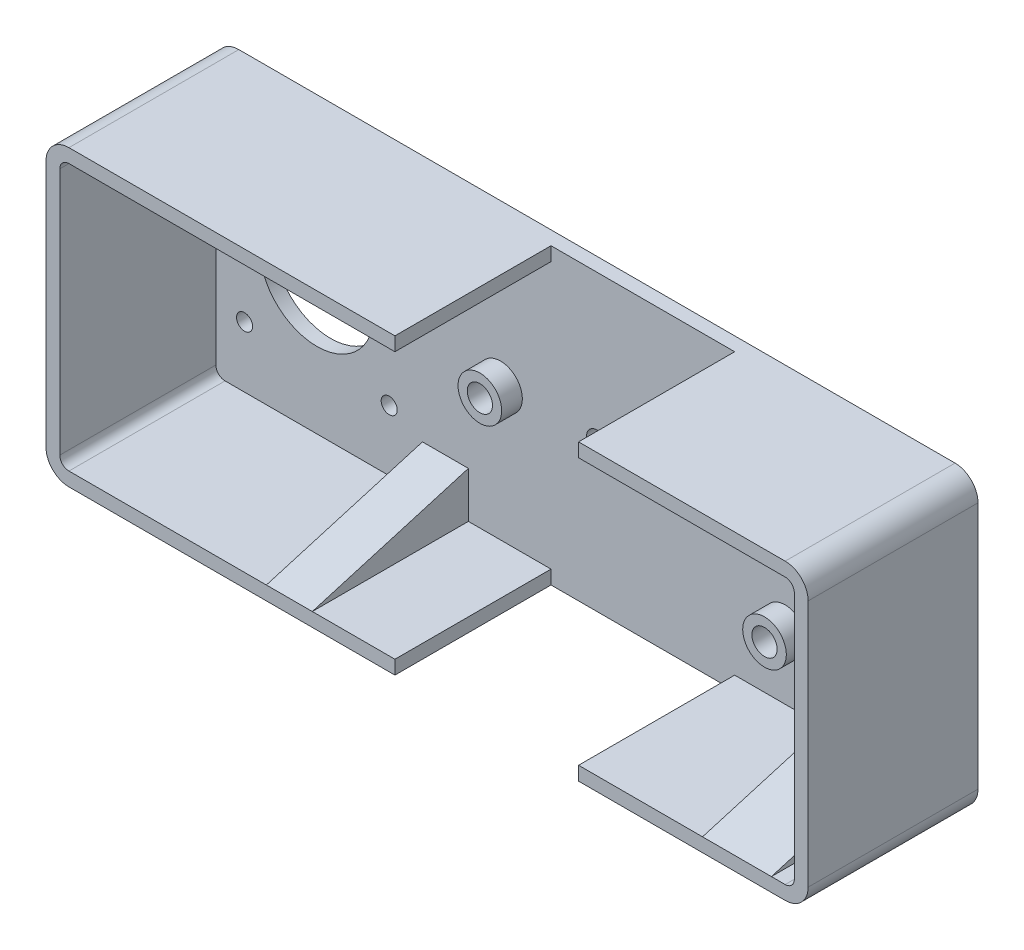
SolidWorks part; units mm, degrees
ref_plane "Front Plane" through (0, 0, 0) normal (0, 0, 1) x (1, 0, 0)
ref_plane "Top Plane" through (0, 0, 0) normal (0, 1, 0) x (1, 0, 0)
ref_plane "Right Plane" through (0, 0, 0) normal (1, 0, 0) x (0, 0, -1)
sketch "Sketch1" plane through (0, 0, 0) normal (0, 0, 1) x (1, 0, 0)
  line L1 (-78, 32) -> (78, 32)
  line L2 (-83, 27) -> (-83, -27)
  line L3 (-78, -32) -> (78, -32)
  line L4 (83, 27) -> (83, -27)
  line L5 (-83, 32) -> (83, -32) construction
  line L6 (-83, -32) -> (83, 32) construction
  arc A0 (78, -32) -> (83, -27) centre (78, -27) ccw
  arc A1 (78, 32) -> (83, 27) centre (78, 27) cw
  arc A2 (-83, -27) -> (-78, -32) centre (-78, -27) ccw
  arc A3 (-78, 32) -> (-83, 27) centre (-78, 27) ccw
  point P0 (0, 0)
  dimension "D3" = 5
  dimension "D1" = 64
  dimension "D2" = 166
extrude "Boss-Extrude1" add sketch "Sketch1" along normal blind 37
sketch "Sketch2" plane through (0, 0, 37) normal (0, 0, 1) x (1, 0, 0)
  line L0 (-58, 0) -> (0, 0) construction
  line L1 (-42.25, 15.75) -> (-73.75, 15.75) construction
  line L2 (-42.25, 15.75) -> (-42.25, -15.75) construction
  line L3 (-42.25, -15.75) -> (-73.75, -15.75) construction
  line L4 (-73.75, 15.75) -> (-73.75, -15.75) construction
  line L5 (-42.25, 15.75) -> (-73.75, -15.75) construction
  line L6 (-42.25, -15.75) -> (-73.75, 15.75) construction
  line L7 (-83, 27) -> (-83, -27) construction
  line L8 (44, 15) -> (44, -15) construction
  line L9 (0, 0) -> (44, 0) construction
  line L10 (44, 0) -> (64, 0) construction
  circle A0 centre (-73.75, 15.75) radius 1.75
  circle A1 centre (-42.25, 15.75) radius 1.75
  circle A2 centre (-73.75, -15.75) radius 1.75
  circle A3 centre (-42.25, -15.75) radius 1.75
  circle A4 centre (-58, 0) radius 12.5
  circle A5 centre (44, 15) radius 2.75
  circle A6 centre (44, -15) radius 2.75
  circle A7 centre (-18, 0) radius 2.75
  circle A8 centre (64, 0) radius 2.25
  point P0 (-58, 0)
  dimension "D1" = 3.5
  dimension "D4" = 25
  dimension "D5" = 5.5
  dimension "D10" = 4.5
  dimension "D2" = 31.5
  dimension "D3" = 25
  dimension "D6" = 30
  dimension "D7" = 127
  dimension "D8" = 62
  dimension "D9" = 20
extrude "Cut-Extrude1" cut sketch "Sketch2" against normal through all
sketch "Sketch3" plane through (0, 0, 37) normal (0, 0, 1) x (1, 0, 0)
  circle A3 centre (44, 15) radius 2.75 construction
  circle A4 centre (44, 15) radius 2.75
  circle A5 centre (44, 15) radius 4.75
  circle A6 centre (-18, 0) radius 2.75 construction
  circle A7 centre (44, -15) radius 2.75 construction
  circle A8 centre (-18, 0) radius 2.75
  circle A9 centre (44, -15) radius 2.75
  circle A10 centre (-18, 0) radius 4.75
  circle A11 centre (44, -15) radius 4.75
  dimension "D1" = 2
  dimension "D2" = 2
sketch "Sketch4" plane through (0, 0, 0) normal (0, 0, 1) x (1, 0, 0)
  line L0 (83, 10) -> (83, -10)
  line L1 (83, -27) -> (83, 27) construction
  line L2 (0, 0) -> (83, 0) construction
  line L3 (83, 10) -> (93, 10)
  line L4 (83, -10) -> (93, -10)
  line L5 (93, 10) -> (93, -10) construction
  arc A0 (93, -10) -> (93, 10) centre (93, 0) ccw
  circle A1 centre (93, 0) radius 2.25
  dimension "D3" = 4.5
  dimension "D1" = 20
  dimension "D2" = 10
sketch "Sketch5" plane through (0, 0, 37) normal (0, 0, 1) x (1, 0, 0)
  line L0 (-18, 0) -> (44, 0) construction
  line L1 (44, 0) -> (44, -15) construction
  circle A0 centre (3, 0) radius 2.25
  circle A1 centre (23, 0) radius 2.25
  point P10 (13, 0)
  dimension "D3" = 4.5
  dimension "D1" = 10
  dimension "D2" = 10
extrude "Cut-Extrude2" cut sketch "Sketch5" against normal through all
sketch "Sketch6" plane through (0, 0, 37) normal (0, 0, 1) x (1, 0, 0)
  line L0 (78, 32) -> (-78, 32) construction
  line L1 (-78, -29) -> (78, -29)
  line L2 (-80, -27) -> (-80, 27)
  line L3 (-78, 29) -> (78, 29)
  line L4 (80, -27) -> (80, 27)
  line L5 (-80, -29) -> (80, 29) construction
  line L6 (-80, 29) -> (80, -29) construction
  line L7 (83, -27) -> (83, 27) construction
  arc A0 (-80, 27) -> (-78, 29) centre (-78, 27) cw
  arc A1 (-78, -29) -> (-80, -27) centre (-78, -27) cw
  arc A2 (78, -29) -> (80, -27) centre (78, -27) ccw
  arc A3 (78, 29) -> (80, 27) centre (78, 27) cw
  point P0 (0, 0)
  dimension "D3" = 2
  dimension "D1" = 3
  dimension "D2" = 3
extrude "Cut-Extrude3" cut sketch "Sketch6" against normal blind 34
sketch "Sketch7" plane through (0, 0, 3) normal (0, 0, 1) x (1, 0, 0)
  circle A0 centre (-18, 0) radius 4.75
  circle A1 centre (-18, 0) radius 2.75 construction
  circle A2 centre (44, -15) radius 4.75
  circle A3 centre (44, 15) radius 4.75
  circle A4 centre (44, -15) radius 2.75 construction
  dimension "D1" = 2
  dimension "D2" = 2
  dimension "D3" = 9.5
extrude "Boss-Extrude2" add sketch "Sketch7" along normal blind 4.5
sketch "Sketch10" plane through (0, 0, 37) normal (0, 0, 1) x (1, 0, 0)
  line L0 (-78, -32) -> (78, -32) construction
  line L1 (-7, -32) -> (33, -32)
  line L2 (-7, -32) -> (-7, 32)
  line L3 (-7, 32) -> (33, 32)
  line L4 (33, -32) -> (33, 32)
  line L5 (-7, -32) -> (33, 32) construction
  line L6 (-7, 32) -> (33, -32) construction
  line L7 (78, 32) -> (-78, 32) construction
  line L8 (13, 0) -> (44, 0) construction
  line L9 (0, 0) -> (83, 0) construction
  line L10 (44, 0) -> (44, -15) construction
  point P0 (13, 0)
  point P20 (80, 10)
  point P22 (77, -9.8749)
  point P25 (0, 0)
  point P26 (0, 0)
  dimension "D1" = 40
  dimension "D2" = 31
extrude "Cut-Extrude4" cut sketch "Sketch10" against normal blind 34
sketch "Sketch11" plane through (0, 0, 7.5) normal (0, 0, 1) x (1, 0, 0)
  circle A0 centre (44, -15) radius 2.75
  circle A1 centre (-18, 0) radius 2.75
  circle A2 centre (44, 15) radius 2.75
  dimension "D1" = 5.5
  dimension "D2" = 5.5
  dimension "D3" = 5.5
extrude "Cut-Extrude5" cut sketch "Sketch11" against normal through all
sketch "Sketch12" plane through (0, 0, 3) normal (0, 0, 1) x (1, 0, 0)
  line L0 (33, -29) -> (78, -29) construction
  line L1 (60, -29) -> (75, -29)
  line L2 (60, -29) -> (60, -19)
  line L3 (60, -19) -> (75, -19)
  line L4 (75, -29) -> (75, -19)
  line L5 (83, 0) -> (32.1507, 0) construction
  line L6 (0, 0) -> (83, 0) construction
  line L7 (60, 19) -> (75, 19)
  line L8 (75, 29) -> (75, 19)
  line L9 (60, 29) -> (75, 29)
  line L10 (60, 29) -> (60, 19)
  line L11 (80, -27) -> (80, 27) construction
  line L12 (80, -6) -> (60, -6)
  line L13 (80, -6) -> (80, -16)
  line L14 (80, -16) -> (60, -16)
  line L15 (60, -6) -> (60, -16)
  line L16 (80, 16) -> (60, 16)
  line L17 (60, 6) -> (60, 16)
  line L18 (80, 6) -> (60, 6)
  line L19 (80, 6) -> (80, 16)
  line L20 (80, -27) -> (80, 27) construction
  line L21 (-78, -29) -> (-7, -29) construction
  line L22 (-35, -29) -> (-25, -29)
  line L23 (-35, -29) -> (-35, -19)
  line L24 (-35, -19) -> (-25, -19)
  line L25 (-25, -29) -> (-25, -19)
  line L26 (-35, 19) -> (-25, 19)
  line L27 (-25, 29) -> (-25, 19)
  line L28 (-35, 29) -> (-25, 29)
  line L29 (-35, 29) -> (-35, 19)
  line L30 (-80, 27) -> (-80, -27) construction
  dimension "D1" = 15
  dimension "D2" = 5
  dimension "D3" = 10
  dimension "D4" = 20
  dimension "D5" = 3
  dimension "D6" = 10
  dimension "D7" = 10
  dimension "D8" = 10
  dimension "D9" = 45
extrude "Boss-Extrude3" add sketch "Sketch12" along normal through all
sketch "Sketch14" plane through (0, -16, 0) normal (0, -1, 0) x (1, 0, 0)
  line L3 (80, 37) -> (60, 37)
  line L4 (60, 37) -> (60, 3)
  line L5 (60, 3) -> (80, 37)
  dimension "D1" = 34
extrude "Cut-Extrude6" cut sketch "Sketch14" against normal blind 33
sketch "Sketch16" plane through (75, 0, 0) normal (1, 0, 0) x (0, 0, -1)
  line L0 (-37, -19) -> (-3, -19)
  line L1 (-3, -19) -> (-37, -29)
  line L2 (-37, -27) -> (-37, 27) construction
  line L3 (-37, -29) -> (-37, -19)
  point P3 (-37, -22.6292)
  point P7 (-37, -34)
  dimension "D1" = 10
  dimension "D2" = 34
extrude "Cut-Extrude8" cut sketch "Sketch16" against normal blind 15
sketch "Sketch17" plane through (60, 0, 0) normal (-1, 0, 0) x (0, 0, 1)
  line L6 (37, 19) -> (3, 19)
  line L7 (3, 19) -> (37, 29)
  line L8 (37, 29) -> (37, 19)
extrude "Cut-Extrude9" cut sketch "Sketch17" against normal blind 15
sketch "Sketch18" plane through (-25, 0, 0) normal (1, 0, 0) x (0, 0, -1)
  line L0 (-37, -29) -> (-37, -19)
  line L1 (-37, -19) -> (-3, -19)
  line L2 (-3, -19) -> (-37, -29)
extrude "Cut-Extrude10" cut sketch "Sketch18" against normal blind 10
sketch "Sketch19" plane through (-25, 0, 0) normal (1, 0, 0) x (0, 0, -1)
  line L0 (-37, 29) -> (-3, 19)
  line L1 (-3, 19) -> (-37, 19)
  line L2 (-37, 19) -> (-37, 29)
extrude "Cut-Extrude11" cut sketch "Sketch19" against normal blind 10
